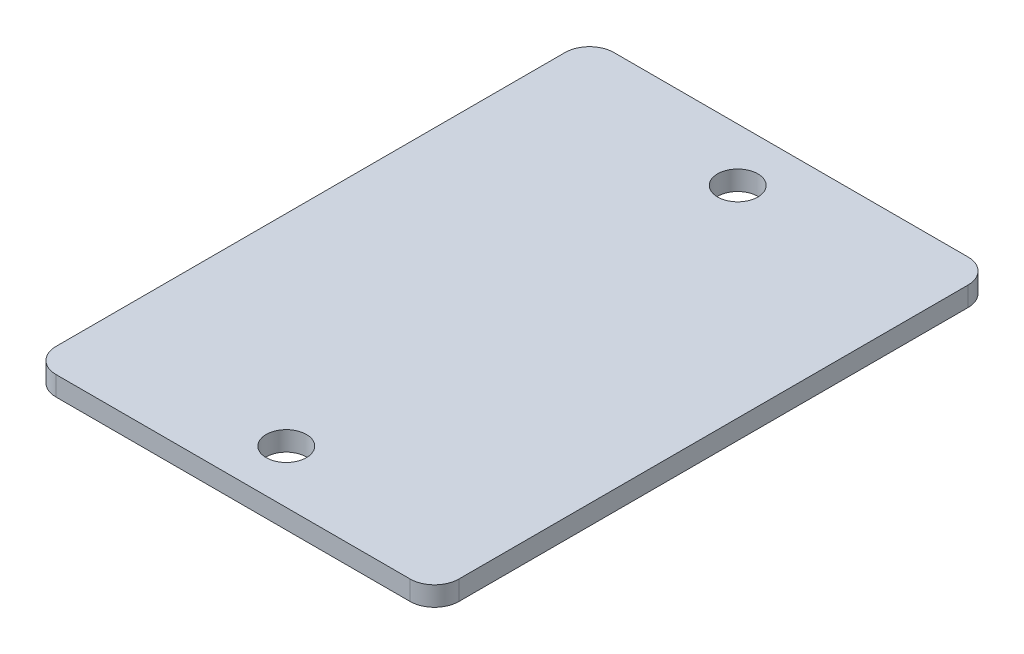
SolidWorks part; units mm, degrees
ref_plane "Front Plane" through (0, 0, 0) normal (0, 0, 1) x (1, 0, 0)
ref_plane "Top Plane" through (0, 0, 0) normal (0, 1, 0) x (1, 0, 0)
ref_plane "Right Plane" through (0, 0, 0) normal (1, 0, 0) x (0, 0, -1)
sketch "Sketch1" plane through (0, 0, 0) normal (0, 1, 0) x (1, 0, 0)
  line L0 (-375.6911, 0) -> (18408.8634, 0) construction
  line L1 (0, -375.6911) -> (0, 18408.8634) construction
  line L3 (-16.51, 22.86) -> (16.51, 22.86)
  line L4 (-16.51, 22.86) -> (-16.51, -22.86)
  line L5 (-16.51, -22.86) -> (16.51, -22.86)
  line L6 (16.51, 22.86) -> (16.51, -22.86)
  line L7 (-16.51, 22.86) -> (16.51, -22.86) construction
  line L8 (-16.51, -22.86) -> (16.51, 22.86) construction
  circle A0 centre (0, 18.5) radius 1.65
  circle A1 centre (0, -18.5) radius 1.65
  point P4 (0, 0)
  dimension "D4" = 3.3
  dimension "D1" = 33.02
  dimension "D2" = 45.72
  dimension "D3" = 37
extrude "Boss-Extrude1" add sketch "Sketch1" along normal blind 1.6
fillet "Fillet1" radius 2 4 edges at (-16.51, 0.8, 22.86) (16.51, 0.8, 22.86) (16.51, 0.8, -22.86) (-16.51, 0.8, -22.86)
equation "\"Frame_Size\" = 220"
equation "\"Frame_Thickness\" = 6"
equation "\"Arm_Width\" = 30"
equation "\"Motor_Mount_Hole_Diameter\" = 8"
equation "\"Motor_Shaft_Diameter\" = 3"
equation "\"Screw_Nut_Diameter\" = 6.5"
equation "\"Screw_Diameter\" = 3"
equation "\"Screw_Shaft_Length\" = 10"
equation "\"Screw_Hole_Separation_C2C\" = 20"
equation "\"Solder_Board_Small_Screw_Hole_Separation\" = 37"
equation "\"Solder_Board_Small_Length\" = 45.72"
equation "\"Solder_Board_Small_Width\" = 33.02"
equation "\"Solder_Board_Small_Thickness\" = 1.6"
equation "\"D1@Sketch1\"=\"Solder_Board_Small_Width\""
equation "\"D2@Sketch1\"=\"Solder_Board_Small_Length\""
equation "\"D3@Sketch1\"=\"Solder_Board_Small_Screw_Hole_Separation\""
equation "\"Solder_Board_Small_Screw_Hole_Diameter\" = 3.3"
equation "\"D4@Sketch1\"=\"Solder_Board_Small_Screw_Hole_Diameter\""
equation "\"D1@Boss-Extrude1\"=\"Solder_Board_Small_Thickness\""
